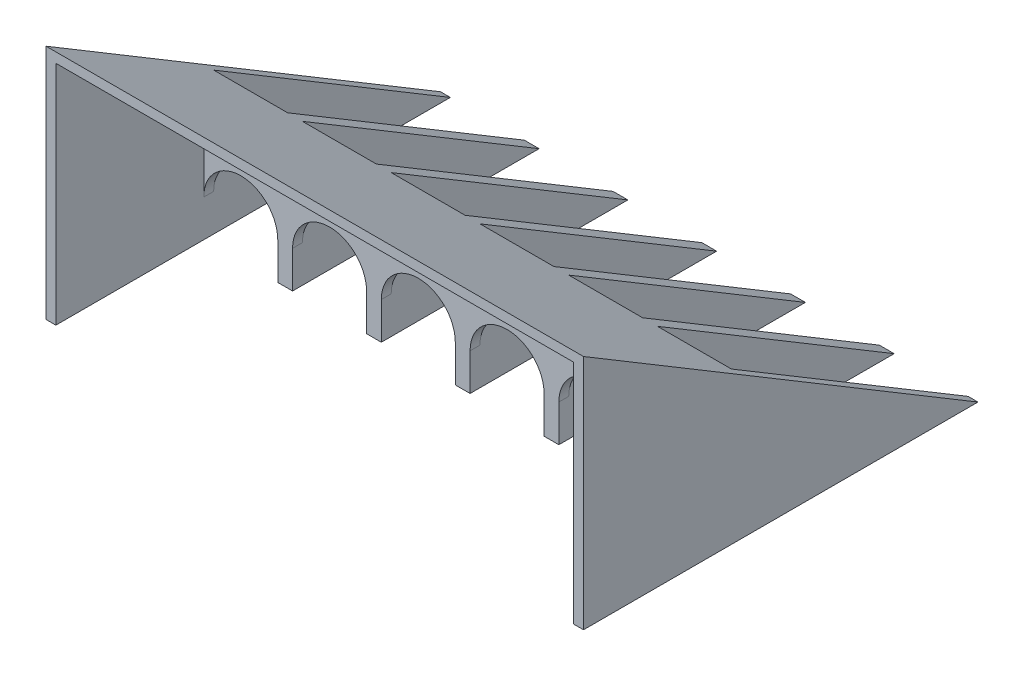
SolidWorks part; units mm, degrees
ref_plane "Alzado" through (0, 0, 0) normal (0, 0, 1) x (1, 0, 0)
ref_plane "Planta" through (0, 0, 0) normal (0, 1, 0) x (1, 0, 0)
ref_plane "Vista lateral" through (0, 0, 0) normal (1, 0, 0) x (0, 0, -1)
sketch "Croquis2" plane through (0, 0, 0) normal (1, 0, 0) x (0, 0, -1)
  line L0 (-60, 36) -> (-60, -60)
  line L1 (-60, -60) -> (100, -60)
  line L2 (100, -60) -> (-60, 36)
  dimension "D1" = 60
  dimension "D2" = 100
  dimension "D3" = 60
extrude "Saliente-Extruir1" add sketch "Croquis2" along normal blind 218
sketch3d "Croquis3D3"
  line L1 (4, -4, 0) -> (214, -4, 0)
  line L2 (4, -4, 0) -> (4, -60, 0)
  line L3 (4, -60, 0) -> (214, -60, 0)
  line L4 (214, -4, 0) -> (214, -60, 0)
  point P4 (0, -60, 0)
  point P5 (0, 36, 0)
  point P6 (218, -60, 0)
  dimension "D1" = 0
  dimension "D2" = 4
  dimension "D3" = 4
  dimension "D4" = 56
sketch "Croquis3" plane through (0, 0, 60) normal (0, 0, 1) x (1, 0, 0)
  line L0 (0, 36) -> (0, -60) construction
  line L1 (4, 32) -> (214, 32)
  line L2 (4, 32) -> (4, -60)
  line L3 (4, -60) -> (214, -60)
  line L4 (214, 32) -> (214, -60)
  line L5 (4, -60) -> (214, -60) construction
  line L6 (218, 36) -> (218, -60) construction
  line L7 (218, 36) -> (0, 36) construction
  dimension "D1" = 4
  dimension "D2" = 0
  dimension "D3" = 4
  dimension "D4" = 4
loft "Cortar-Recubrir1" cut profiles "Croquis3", "Croquis3D3"
sketch "Croquis4" plane through (0, -60, 0) normal (0, -1, 0) x (1, 0, 0)
  line L0 (218, -100) -> (0, -100) construction
  line L1 (214, 0) -> (4, 0) construction
  line L2 (4, 0) -> (214, 0) construction
  line L3 (4, -4) -> (34, -4)
  line L4 (4, -4) -> (4, -100)
  line L5 (4, -100) -> (34, -100)
  line L6 (34, -4) -> (34, -100)
  line L7 (0, 60) -> (0, -100) construction
  line L8 (40, -4) -> (70, -4)
  line L9 (40, -4) -> (40, -100)
  line L10 (40, -100) -> (70, -100)
  line L11 (70, -4) -> (70, -100)
  line L12 (76, -4) -> (106, -4)
  line L13 (76, -4) -> (76, -100)
  line L14 (76, -100) -> (106, -100)
  line L15 (106, -4) -> (106, -100)
  line L16 (112, -4) -> (142, -4)
  line L17 (112, -4) -> (112, -100)
  line L18 (112, -100) -> (142, -100)
  line L19 (142, -4) -> (142, -100)
  line L20 (184, -4) -> (214, -4)
  line L21 (184, -4) -> (184, -100)
  line L22 (184, -100) -> (214, -100)
  line L23 (214, -4) -> (214, -100)
  line L24 (218, 60) -> (218, -100) construction
  line L25 (148, -4) -> (178, -4)
  line L26 (178, -4) -> (178, -100)
  line L27 (178, -100) -> (148, -100)
  line L28 (148, -100) -> (148, -4)
  point P0 (34, 0)
  point P1 (214, 0)
  point P2 (4, 0)
  point P6 (184, 0)
  point P8 (142, 0)
  point P11 (46.5, 0)
  point P12 (70, 0)
  point P13 (131.1346, 0)
  point P14 (89, 0)
  point P15 (106, 0)
  dimension "D2" = 30
  dimension "D3" = 4
  dimension "D4" = 30
  dimension "D5" = 30
  dimension "D6" = 30
  dimension "D7" = 6
  dimension "D8" = 30
  dimension "D9" = 6
  dimension "D10" = 4
  dimension "D11" = 4
  dimension "D12" = 4
  dimension "D13" = 4
  dimension "D14" = 4
  dimension "D15" = 6
  dimension "D16" = 4
  dimension "D17" = 42
  dimension "D18" = 6
  dimension "D19" = 30
  dimension "D20" = 6
extrude "Cortar-Extruir1" cut sketch "Croquis4" against normal blind 60
sketch "Croquis5" plane through (0, 0, -4) normal (0, 0, -1) x (-1, 0, 0)
  line L0 (-199, -60) -> (-184, -60)
  line L1 (-214, -60) -> (-184, -60) construction
  line L2 (-184, -60) -> (-184, -30)
  line L3 (-184, -30) -> (-214, -30)
  line L4 (-214, -30) -> (-214, -60)
  line L5 (-214, -60) -> (-199, -60)
  line L6 (-163, -60) -> (-148, -60)
  line L7 (-178, -60) -> (-148, -60) construction
  line L8 (-148, -60) -> (-148, -30)
  line L9 (-148, -30) -> (-178, -30)
  line L10 (-178, -30) -> (-178, -60)
  line L11 (-178, -60) -> (-163, -60)
  line L12 (-127, -60) -> (-112, -60)
  line L13 (-142, -60) -> (-112, -60) construction
  line L14 (-112, -60) -> (-112, -30)
  line L15 (-112, -30) -> (-142, -30)
  line L16 (-142, -30) -> (-142, -60)
  line L17 (-142, -60) -> (-127, -60)
  line L18 (-91, -60) -> (-76, -60)
  line L19 (-106, -60) -> (-76, -60) construction
  line L20 (-76, -60) -> (-76, -30)
  line L21 (-76, -30) -> (-106, -30)
  line L22 (-106, -30) -> (-106, -60)
  line L23 (-106, -60) -> (-91, -60)
  line L24 (-55, -60) -> (-40, -60)
  line L25 (-70, -60) -> (-40, -60) construction
  line L26 (-40, -60) -> (-40, -30)
  line L27 (-40, -30) -> (-70, -30)
  line L28 (-70, -30) -> (-70, -60)
  line L29 (-70, -60) -> (-55, -60)
  line L30 (-19, -60) -> (-4, -60)
  line L31 (-34, -60) -> (-4, -60) construction
  line L32 (-4, -60) -> (-4, -30)
  line L33 (-4, -30) -> (-34, -30)
  line L34 (-34, -30) -> (-34, -60)
  line L35 (-34, -60) -> (-19, -60)
  dimension "D1" = 15
  dimension "D2" = 15
  dimension "D3" = 30
  dimension "D4" = 15
  dimension "D5" = 15
  dimension "D6" = 30
  dimension "D7" = 15
  dimension "D8" = 15
  dimension "D9" = 30
  dimension "D10" = 15
  dimension "D11" = 15
  dimension "D12" = 30
  dimension "D13" = 15
  dimension "D14" = 15
  dimension "D15" = 30
  dimension "D16" = 15
  dimension "D17" = 15
  dimension "D18" = 30
extrude "Cortar-Extruir2" cut sketch "Croquis5" against normal blind 10
fillet "Redondeo1" radius 15 12 edges at (34, -30, -2) (40, -30, -2) (70, -30, -2) (76, -30, -2) (106, -30, -2) (112, -30, -2) (142, -30, -2) (148, -30, -2) (178, -30, -2) (184, -30, -2)
